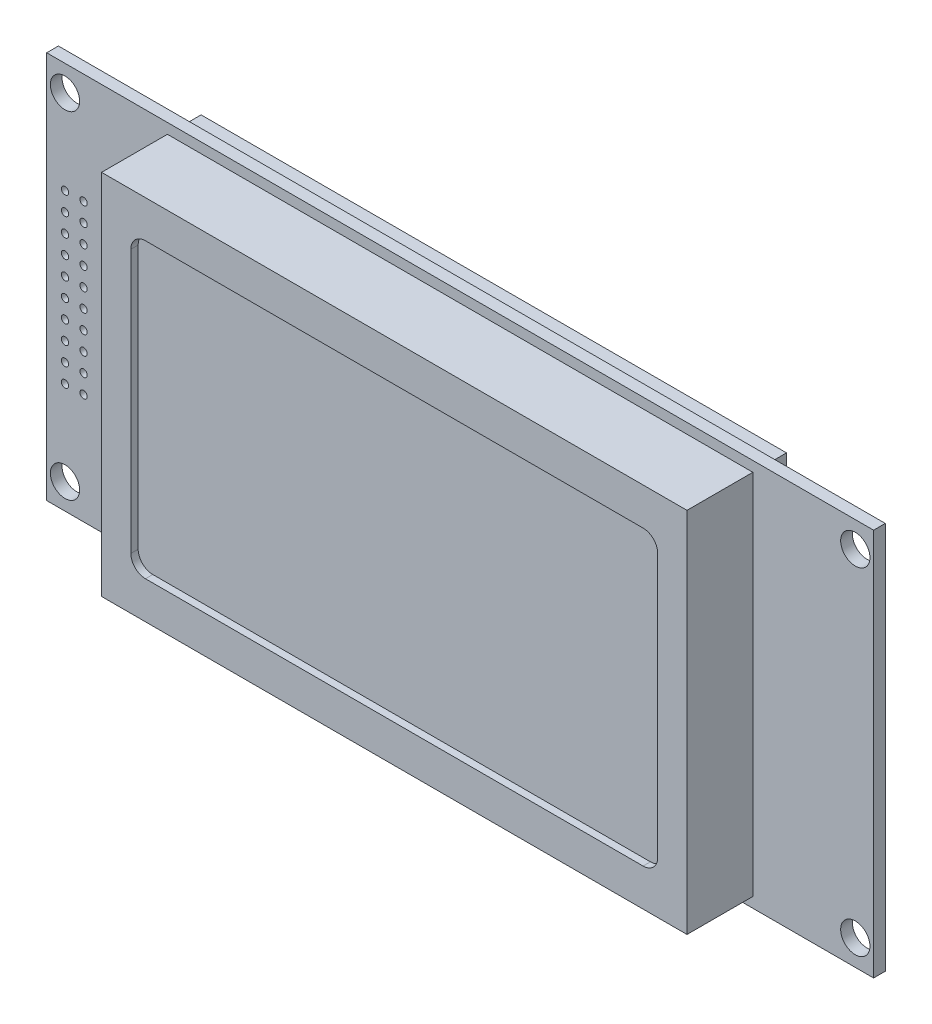
SolidWorks part; units mm, degrees
ref_plane "Plan de face" through (0, 0, 0) normal (0, 0, 1) x (1, 0, 0)
ref_plane "Plan de dessus" through (0, 0, 0) normal (0, 1, 0) x (1, 0, 0)
ref_plane "Plan de droite" through (0, 0, 0) normal (1, 0, 0) x (0, 0, -1)
sketch "Esquisse1" plane through (0, 0, 0) normal (0, 0, 1) x (1, 0, 0)
  line L0 (-56.5, 0) -> (56.5, 0) construction
  line L1 (-56.5, 26.5) -> (56.5, 26.5)
  line L2 (-56.5, 26.5) -> (-56.5, -26.5)
  line L3 (-56.5, -26.5) -> (56.5, -26.5)
  line L4 (56.5, 26.5) -> (56.5, -26.5)
  line L5 (0, 26.5) -> (0, -26.5) construction
  line L6 (-54, 23) -> (-54, -23) construction
  line L7 (-54, -23) -> (54, -23) construction
  circle A0 centre (-54, 23) radius 2
  circle A1 centre (-54, -23) radius 2
  circle A2 centre (54, -23) radius 2
  circle A3 centre (54, 23) radius 2
  circle A4 centre (-54, 11.43) radius 0.5
  circle A5 centre (-51.46, 11.43) radius 0.5
  circle A6 centre (-51.46, 8.89) radius 0.5
  circle A7 centre (-51.46, 6.35) radius 0.5
  circle A8 centre (-51.46, 3.81) radius 0.5
  circle A9 centre (-51.46, 1.27) radius 0.5
  circle A10 centre (-51.46, -1.27) radius 0.5
  circle A11 centre (-51.46, -3.81) radius 0.5
  circle A12 centre (-51.46, -6.35) radius 0.5
  circle A13 centre (-51.46, -8.89) radius 0.5
  circle A14 centre (-51.46, -11.43) radius 0.5
  circle A15 centre (-54, 8.89) radius 0.5
  circle A16 centre (-54, 6.35) radius 0.5
  circle A17 centre (-54, 3.81) radius 0.5
  circle A18 centre (-54, 1.27) radius 0.5
  circle A19 centre (-54, -1.27) radius 0.5
  circle A20 centre (-54, -3.81) radius 0.5
  circle A21 centre (-54, -6.35) radius 0.5
  circle A22 centre (-54, -8.89) radius 0.5
  circle A23 centre (-54, -11.43) radius 0.5
  point P10 (-54, 0)
  point P11 (0, -23)
  point P20 (0, 0)
  dimension "D5" = 4
  dimension "D7" = 1
  dimension "D1" = 53
  dimension "D2" = 113
  dimension "D3" = 46
  dimension "D4" = 108
  dimension "D6" = 2.5
  dimension "D8" = 11.43
  dimension "D11" = 108
  dimension "D9" = 2
  dimension "D10" = 10
extrude "Boss.-Extru.1" add sketch "Esquisse1" along normal blind 1.6
sketch "Esquisse2" plane through (0, 0, 1.6) normal (0, 0, 1) x (1, 0, 0)
  line L0 (0, 26.5) -> (0, -26.5) construction
  line L1 (56.5, 26.5) -> (-56.5, 26.5) construction
  line L2 (-56.5, -26.5) -> (56.5, -26.5) construction
  line L4 (-40, -25.1) -> (40, -25.1)
  line L5 (-40, -25.1) -> (-40, 25.1)
  line L6 (-40, 25.1) -> (40, 25.1)
  line L7 (40, -25.1) -> (40, 25.1)
  line L8 (-40, -25.1) -> (40, 25.1) construction
  line L9 (-40, 25.1) -> (40, -25.1) construction
  point P7 (0, 0)
  dimension "D1" = 50.2
  dimension "D2" = 80
extrude "Boss.-Extru.2" add sketch "Esquisse2" along normal blind 9
sketch "Esquisse4" plane through (0, 0, 10.6) normal (0, 0, 1) x (1, 0, 0)
  line L1 (34, -20) -> (-34, -20)
  line L2 (36, -18) -> (36, 18)
  line L3 (34, 20) -> (-34, 20)
  line L4 (-36, -18) -> (-36, 18)
  line L5 (36, -20) -> (-36, 20) construction
  line L6 (36, 20) -> (-36, -20) construction
  arc A0 (-34, -20) -> (-36, -18) centre (-34, -18) cw
  arc A1 (34, -20) -> (36, -18) centre (34, -18) ccw
  arc A2 (36, 18) -> (34, 20) centre (34, 18) ccw
  arc A3 (-34, 20) -> (-36, 18) centre (-34, 18) ccw
  point P0 (0, 0)
  dimension "D3" = 2
  dimension "D1" = 72
  dimension "D2" = 40
extrude "Enlèv. mat.-Extru.1" cut sketch "Esquisse4" against normal blind 1
sketch "Esquisse6" plane through (0, 0, 0) normal (0, 0, -1) x (-1, 0, 0)
  line L1 (-40, 25.1) -> (40, 25.1)
  line L2 (-40, 25.1) -> (-40, 22.6716)
  line L3 (-40, 22.6716) -> (40, 22.6716)
  line L4 (40, 25.1) -> (40, 22.6716)
  line L5 (-40, -25.1) -> (40, -25.1)
  line L6 (-40, -25.1) -> (-40, -23.3251)
  line L7 (-40, -23.3251) -> (40, -23.3251)
  line L8 (40, -25.1) -> (40, -23.3251)
  point P9 (0, 0)
  point P11 (0, 0)
  point P13 (0, 0)
  point P15 (0, 0)
extrude "Boss.-Extru.3" add sketch "Esquisse6" along normal blind 3
equation "\"D8@Esquisse1\"=22.86/2"
